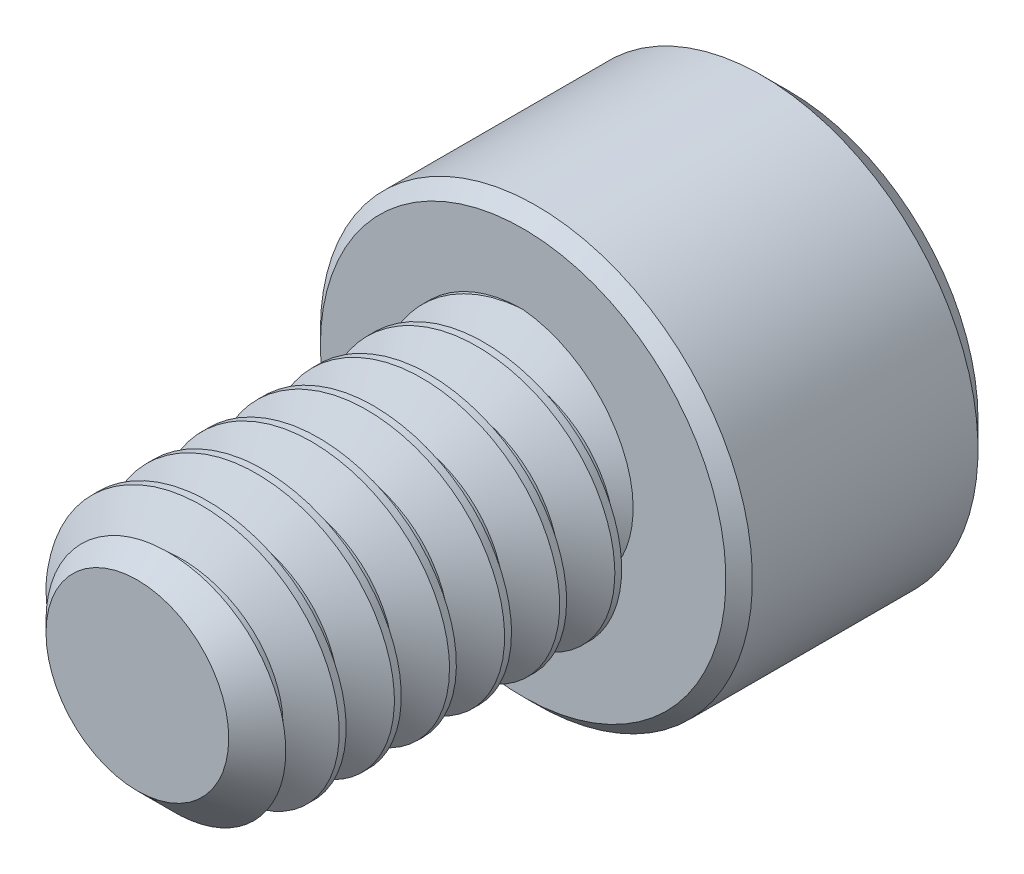
SolidWorks part; units mm, degrees
material "Plain Carbon Steel"
ref_plane "Front Plane" through (0, 0, 0) normal (0, 0, 1) x (1, 0, 0)
ref_plane "Top Plane" through (0, 0, 0) normal (0, 1, 0) x (1, 0, 0)
ref_plane "Right Plane" through (0, 0, 0) normal (1, 0, 0) x (0, 0, -1)
sketch "Sketch1" plane through (0, 0, 0) normal (0, 0, 1) x (1, 0, 0)
  line L0 (0, 1.0922) -> (0, -1.0922) construction
  circle A0 centre (0, 0) radius 1.0922
  dimension "OD" = 2.1844
extrude "Extrude1" add sketch "Sketch1" against normal blind 3.175
sketch "Sketch2" plane through (0, 0, 0) normal (0, 0, 1) x (1, 0, 0)
  circle A0 centre (0, 0) radius 1.0922 construction
  circle A1 centre (0, 0) radius 1.0922
curve "Helix/Spiral1" pitch 0.4536 height 3.6286 radius 1.0922 centre (0, 0, 0) axis (0, 0, -1) start towards (0, 1, 0) parameters "pitch"=0.4536
chamfer "Chamfer3" distance 0.3402 angle 45 1 edges at (1.0922, 0, 0)
sketch "Sketch3" plane through (0, 0, 0) normal (1, 0, 0) x (0, 0, -1)
  line L0 (-0.3969, 1.0922) -> (-0.2268, 0.7976)
  line L1 (-0.2268, 0.7976) -> (-0.1701, 0.7976)
  line L2 (-0.1701, 0.7976) -> (0, 1.0922)
  line L3 (-0.3969, 1.0922) -> (0, 1.0922)
  line L4 (-0.1984, 1.0922) -> (-0.1984, 0.7976) construction
  line L5 (-0.3118, 0.9449) -> (-0.085, 0.9449) construction
  line L6 (0, 1.0922) -> (0, -1.0922) construction
  dimension "D1" = 0.0567
  dimension "D2" = 0.2268
  dimension "D3" = 60
sweep "Cut-Sweep1" cut profiles "Sketch3" path "Helix/Spiral1" align with end faces yes
sketch "Sketch6" plane through (0, 0, -3.175) normal (0, 0, -1) x (-1, 0, 0)
  circle A0 centre (0, 0) radius 1.778
  dimension "head dia" = 3.556
extrude "Extrude2" add sketch "Sketch6" along normal blind 2.1844
sketch "Sketch7" plane through (0, 0, -5.3594) normal (0, 0, -1) x (-1, 0, 0)
  line L1 (0, 1.1457) -> (-0.9922, 0.5728)
  line L2 (-0.9922, 0.5728) -> (-0.9922, -0.5728)
  line L3 (-0.9922, -0.5728) -> (0, -1.1457)
  line L4 (0, -1.1457) -> (0.9922, -0.5728)
  line L5 (0.9922, -0.5728) -> (0.9922, 0.5728)
  line L6 (0.9922, 0.5728) -> (0, 1.1457)
  circle A0 centre (0, 0) radius 0.9922 construction
  dimension "hex dia" = 1.9844
extrude "Cut-Extrude1" cut sketch "Sketch7" against normal blind 1.4883
sketch "Sketch8" plane through (0, 0, -5.3594) normal (0, 0, -1) x (-1, 0, 0)
  circle A0 centre (0, 0) radius 1.1457
extrude "Cut-Extrude2" cut sketch "Sketch8" against normal blind 0.2184 draft 45
chamfer "Chamfer1" distance 0.2184 angle 45 1 edges at (-1.778, 0, -5.3594)
chamfer "Chamfer2" distance 0.1092 angle 45 1 edges at (-1.778, 0, -3.175)
sketch "Sketch9" plane through (0, 0, 0) normal (1, 0, 0) x (0, 0, -1)
  line L0 (0, 1.0922) -> (0, -1.0922) construction
  line L1 (2.4946, 1.0922) -> (2.4946, -1.0922) construction
  line L2 (3.175, 1.778) -> (3.175, -1.778) construction
  line L3 (5.3594, 1.778) -> (5.3594, -1.778) construction
  line L4 (5.3594, 0) -> (0, 0) construction
  dimension "D1" = 2.4946
  dimension "D2" = 2.1844
  dimension "D3" = 3.556
  dimension "D4" = 3.175
equation "\"D3@Helix/Spiral1\" = \"screw length@Extrude1\"+\"pitch@Helix/Spiral1\""
equation "\"D1@Sketch3\" = \"pitch@Helix/Spiral1\"*.125"
equation "\"D2@Sketch3\" = \"pitch@Helix/Spiral1\"*.5"
equation "\"D1@Cut-Extrude1\" = \"hex dia@Sketch7\"*.75"
equation "\"D1@Chamfer1\" = \"head depth@Extrude2\"/10"
equation "\"D1@Sketch9\" = \"pitch@Helix/Spiral1\"*5.5"
equation "\"D1@Chamfer2\" = \"D1@Chamfer1\"/2"
equation "\"D1@Cut-Extrude2\" = \"D1@Chamfer2\"*2"
equation "\"D1@Chamfer3\" = \"pitch@Helix/Spiral1\"*.750"
equation "\"D2@Sketch9\" = \"head depth@Extrude2\""
equation "\"D3@Sketch9\" = \"head dia@Sketch6\""
equation "\"D4@Sketch9\" = \"screw length@Extrude1\""
